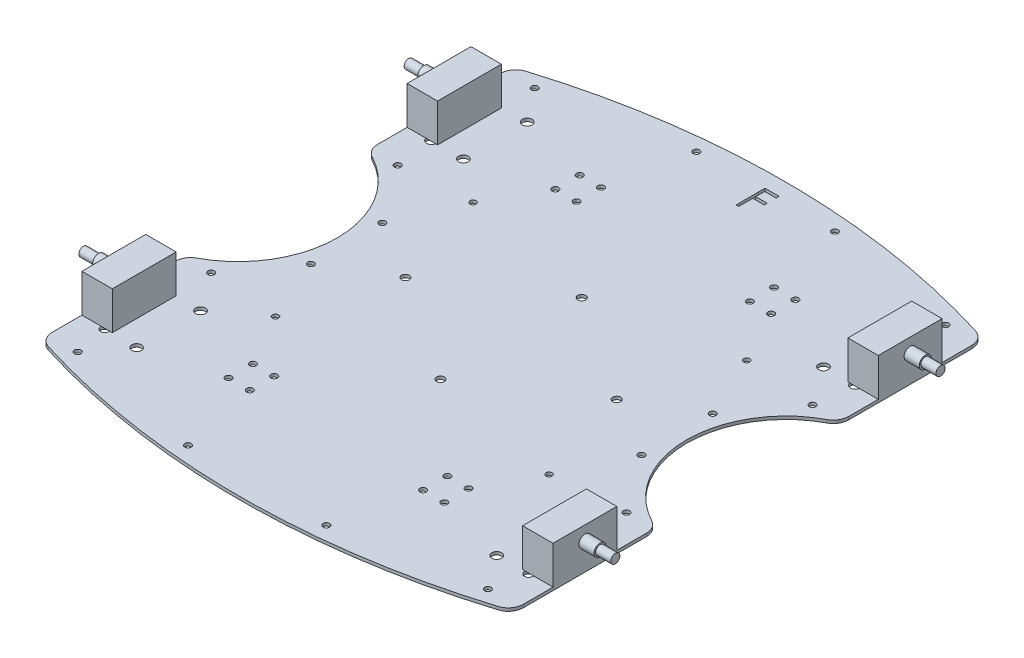
SolidWorks part; units mm, degrees
material "1060 Alloy"
ref_plane "Front Plane" through (0, 0, 0) normal (0, 0, 1) x (1, 0, 0)
ref_plane "Top Plane" through (0, 0, 0) normal (0, 1, 0) x (1, 0, 0)
ref_plane "Right Plane" through (0, 0, 0) normal (1, 0, 0) x (0, 0, -1)
sketch "Sketch1" plane through (0, 0, 0) normal (0, 1, 0) x (1, 0, 0)
  line L0 (-155, 147.4962) -> (-155, 66.5225)
  line L1 (-155, 60.21) -> (-115, 60.21)
  line L2 (-115, 60.21) -> (-115, -60.21)
  line L3 (-115, -60.21) -> (-155, -60.21)
  line L4 (-155, -66.5225) -> (-155, -147.4962)
  line L5 (-155, -154.81) -> (155, -154.81)
  line L6 (155, -147.4962) -> (155, -66.5225)
  line L7 (155, -60.21) -> (115, -60.21)
  line L8 (115, -60.21) -> (115, 60.21)
  line L9 (115, 60.21) -> (155, 60.21)
  line L10 (155, 66.5225) -> (155, 147.4962)
  line L11 (155, 154.81) -> (-155, 154.81)
  line L12 (0, 154.81) -> (0, 0) construction
  line L13 (0, 0) -> (100, 0) construction
  arc A0 (-147.9592, 157.0483) -> (147.9592, 157.0483) centre (0, -320.5583) cw
  arc A1 (-147.9592, -157.0483) -> (147.9592, -157.0483) centre (0, 320.5583) ccw
  arc A2 (-149.689, 57.69) -> (-149.689, -57.69) centre (-180.3156, 0) cw
  arc A3 (149.689, 57.69) -> (149.689, -57.69) centre (180.3156, 0) ccw
  arc A4 (-155, 66.5225) -> (-149.689, 57.69) centre (-145, 66.5225) ccw
  arc A5 (-149.689, -57.69) -> (-155, -66.5225) centre (-145, -66.5225) ccw
  arc A6 (-155, -147.4962) -> (-147.9592, -157.0483) centre (-145, -147.4962) ccw
  arc A7 (147.9592, -157.0483) -> (155, -147.4962) centre (145, -147.4962) ccw
  arc A8 (155, -66.5225) -> (149.689, -57.69) centre (145, -66.5225) ccw
  arc A9 (149.689, 57.69) -> (155, 66.5225) centre (145, 66.5225) ccw
  arc A10 (155, 147.4962) -> (147.9592, 157.0483) centre (145, 147.4962) ccw
  arc A11 (-155, 147.4962) -> (-147.9592, 157.0483) centre (-145, 147.4962) cw
  circle A12 centre (-139.47, 128.51) radius 2.75
  circle A14 centre (-139.47, 86.51) radius 3.1997
  circle A16 centre (139.47, 86.51) radius 3.1997
  circle A19 centre (139.47, 128.51) radius 2.75
  circle A20 centre (139.47, -86.51) radius 3.1997
  circle A22 centre (139.47, -128.51) radius 2.75
  circle A25 centre (-139.47, -86.51) radius 3.1997
  circle A27 centre (-139.47, -128.51) radius 2.75
  circle A28 centre (-70.97, 115.51) radius 2.125
  circle A29 centre (-56.97, 115.51) radius 2.125
  circle A30 centre (-70.97, 99.51) radius 2.125
  circle A31 centre (-56.97, 99.51) radius 2.125
  circle A32 centre (56.97, 99.51) radius 2.125
  circle A33 centre (70.97, 99.51) radius 2.125
  circle A34 centre (56.97, 115.51) radius 2.125
  circle A35 centre (70.97, 115.51) radius 2.125
  circle A36 centre (70.97, -99.51) radius 2.125
  circle A37 centre (56.97, -99.51) radius 2.125
  circle A38 centre (70.97, -115.51) radius 2.125
  circle A39 centre (56.97, -115.51) radius 2.125
  circle A40 centre (-56.97, -99.51) radius 2.125
  circle A41 centre (-70.97, -99.51) radius 2.125
  circle A42 centre (-56.97, -115.51) radius 2.125
  circle A43 centre (-70.97, -115.51) radius 2.125
  circle A44 centre (-118.47, 128.51) radius 3.1997
  circle A45 centre (-118.47, 86.51) radius 3.1997
  circle A46 centre (118.47, 86.51) radius 3.1997
  circle A47 centre (118.47, 128.51) radius 3.1997
  circle A48 centre (118.47, -128.51) radius 3.1997
  circle A49 centre (118.47, -86.51) radius 3.1997
  circle A50 centre (-118.47, -86.51) radius 3.1997
  circle A51 centre (-118.47, -128.51) radius 3.1997
  circle A60 centre (-0.51, 46.4) radius 2.6
  circle A61 centre (68.99, -0.1) radius 2.6
  circle A62 centre (-0.51, -46.6) radius 2.6
  circle A63 centre (-70.01, -0.1) radius 2.6
  circle A64 centre (-90.51, 64.9) radius 2
  circle A65 centre (89.49, 64.9) radius 2
  circle A66 centre (89.49, -65.1) radius 2
  circle A67 centre (-90.51, -65.1) radius 2
  point P14 (0, 154.81)
  dimension "D6" = 154.81
  dimension "D8" = 500
  dimension "D9" = 500
  dimension "D10" = 10
  dimension "D11" = 5.5
  dimension "D13" = 4.25
  dimension "D1" = 310
  dimension "D2" = 230
  dimension "D3" = 115
  dimension "D4" = 94.6
  dimension "D5" = 94.6
  dimension "D7" = 154.81
  dimension "D12" = 100
extrude "Boss-Extrude1" add sketch "Sketch1" along normal blind 2 contours A11 L11 A10 A0 | A11 L0 A4 L1 L2 L3 A5 L4 A6 L5 A7 L6 A8 L7 L8 L9 A9 L10 A10 L11 | A1 A7 L5 A6 | L1 A4 A2 L2 | A2 A5 L3 L2 | A3 A9 L9 L8 | L7 A8 A3 L8 region at (0.0008, 0, -0.0002) region at (0, 0, -164.6942) region at (-125.8472, 0, -46.1824) region at (-125.8472, 0, 46.1824) region at (125.8472, 0, -46.1824) region at (125.8472, 0, 46.1824) region at (0, 0, 164.6942)
sketch "Sketch2" plane through (0, 2, 0) normal (0, 1, 0) x (1, 0, 0)
  text T0 "F" font "Century Gothic" height in points 72
  dimension "D1" = 5
  dimension "D2" = 150
extrude "Cut-Extrude1" cut sketch "Sketch2" against normal through all
sketch "Sketch3" plane through (0, 2, 0) normal (0, 1, 0) x (1, 0, 0)
  line L0 (0, 164.4417) -> (0, -164.4417) construction
  line L1 (0, 0) -> (100, 0) construction
  arc A0 (-143.5204, 142.7201) -> (143.5204, 142.7201) centre (0, -320.5583) cw construction
  arc A1 (-145, 147.4962) -> (145, 147.4962) centre (0, -320.5583) cw construction
  circle A2 centre (-135.4182, 150.3578) radius 2.125
  circle A3 centre (-45.9141, 167.2859) radius 2.125
  circle A4 centre (45.1768, 167.3547) radius 2.125
  circle A5 centre (134.7064, 150.5619) radius 2.125
  arc A6 (-143.5204, -142.7201) -> (143.5204, -142.7201) centre (0, 320.5583) ccw construction
  circle A7 centre (134.7064, -150.5619) radius 2.125
  circle A8 centre (45.1768, -167.3547) radius 2.125
  circle A9 centre (-45.9141, -167.2859) radius 2.125
  circle A10 centre (-135.4182, -150.3578) radius 2.125
  arc A11 (-142.6555, 70.9388) -> (-142.6555, -70.9388) centre (-180.3156, 0) cw construction
  arc A12 (-145, 66.5225) -> (-145, -66.5225) centre (-180.3156, 0) cw construction
  circle A13 centre (-136.4983, 61.2575) radius 2.125
  circle A14 centre (-108.7231, 23.3871) radius 2.125
  circle A15 centre (-108.7854, -23.577) radius 2.125
  circle A16 centre (-136.661, -61.3735) radius 2.125
  circle A17 centre (136.661, -61.3735) radius 2.125
  circle A18 centre (108.7854, -23.577) radius 2.125
  circle A19 centre (108.7231, 23.3871) radius 2.125
  circle A20 centre (136.4983, 61.2575) radius 2.125
  arc A21 (145, 66.5225) -> (145, -66.5225) centre (180.3156, 0) ccw construction
  arc A22 (142.6555, 70.9388) -> (142.6555, -70.9388) centre (180.3156, 0) ccw construction
  arc A23 (-145, -147.4962) -> (145, -147.4962) centre (0, 320.5583) ccw construction
  point P16 (30.0958, -234.0277)
  point P46 (-150.2197, 86.5306)
  dimension "D1" = 490
  dimension "D2" = 4.25
  dimension "D4" = 485
  dimension "D5" = 80.3156
  dimension "D7" = 100
  dimension "D3" = 10
  dimension "D6" = 10
  dimension "D8" = 328.8834
extrude "Cut-Extrude2" cut sketch "Sketch3" against normal through all
sketch "Sketch4" plane through (0, 2, 0) normal (0, 1, 0) x (1, 0, 0)
  line L0 (-118.47, 128.51) -> (-118.47, 86.51)
  line L1 (-118.47, -86.51) -> (-118.47, -128.51)
  line L2 (-118.47, 107.51) -> (-155, 107.0094)
  line L3 (-155, 147.4962) -> (-155, 66.5225) construction
  line L4 (-118.47, -107.51) -> (-155, -107.0094)
  line L5 (-155, -66.5225) -> (-155, -147.4962) construction
sketch "Sketch5" plane through (-155, 0, 0) normal (-1, 0, 0) x (0, 0, 1)
  line L0 (-128.51, 2) -> (-86.51, 2) construction
  line L1 (-128.0094, 2) -> (-86.0094, 2)
  line L2 (-128.0094, 2) -> (-128.0094, 27)
  line L3 (-128.0094, 27) -> (-86.0094, 27)
  line L4 (-86.0094, 2) -> (-86.0094, 27)
  line L5 (-147.4962, 0) -> (-66.5225, 0) construction
  line L6 (66.5225, 2) -> (147.4962, 2) construction
  line L7 (86.0094, 2) -> (128.0094, 2)
  line L8 (86.0094, 2) -> (86.0094, 27)
  line L9 (86.0094, 27) -> (128.0094, 27)
  line L10 (128.0094, 2) -> (128.0094, 27)
  line L11 (66.5225, 0) -> (147.4962, 0) construction
  point P8 (-107.0094, 0)
  point P9 (-107.0094, 2)
  point P18 (107.0094, 0)
  point P19 (107.0094, 2)
  dimension "D1" = 25
  dimension "D2" = 42
  dimension "D3" = 42
  dimension "D4" = 25
extrude "Boss-Extrude2" add sketch "Sketch5" against normal blind 20
extrude "Boss-Extrude3" add sketch "Sketch5<2>" along normal blind 20 from surface starting at face at (155, 1, 107.0094)
sketch "Sketch5<2>" plane through (-155, 0, 0) normal (-1, 0, 0) x (0, 0, 1) same geometry as "Sketch5"
sketch "Sketch6" plane through (-155, 0, 0) normal (-1, 0, 0) x (0, 0, 1)
  line L0 (86.51, 2) -> (128.51, 2) construction
  line L1 (128.0094, 2) -> (128.0094, 27) construction
  line L3 (-128.0094, 27) -> (-128.0094, 2) construction
  line L4 (-128.51, 2) -> (-86.51, 2) construction
  circle A0 centre (107.0094, 17.75) radius 4
  circle A1 centre (-107.0094, 17.75) radius 4
  dimension "D1" = 8
  dimension "D2" = 15.75
  dimension "D3" = 21
  dimension "D4" = 8
  dimension "D5" = 21
  dimension "D6" = 15.75
extrude "Boss-Extrude4" add sketch "Sketch6" along normal blind 10
sketch "Sketch7" plane through (-165, 0, 0) normal (-1, 0, 0) x (0, 0, 1)
  circle A0 centre (107.0094, 17.75) radius 3
  circle A1 centre (-107.0094, 17.75) radius 3
  dimension "D1" = 6
  dimension "D2" = 6
extrude "Boss-Extrude5" add sketch "Sketch7" along normal blind 10
ref_plane "Plane1" through (0, 0, 0) normal (-1, 0, 0) x (0, 0, 1)
mirror "Mirror1" about plane through (0, 0, 0) normal (-1, 0, 0) of "Boss-Extrude5", "Boss-Extrude4"
